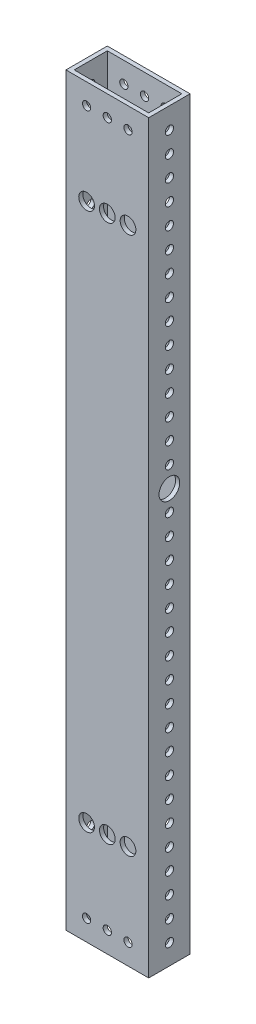
SolidWorks part; units mm, degrees
ref_plane "Front Plane" through (0, 0, 0) normal (0, 0, 1) x (1, 0, 0)
ref_plane "Top Plane" through (0, 0, 0) normal (0, 1, 0) x (1, 0, 0)
ref_plane "Right Plane" through (0, 0, 0) normal (1, 0, 0) x (0, 0, -1)
sketch "Sketch1" plane through (0, 0, 0) normal (0, 1, 0) x (1, 0, 0)
  line L1 (-46.8721, 24.2038) -> (3.9279, 24.2038)
  line L2 (-46.8721, 24.2038) -> (-46.8721, -1.1962)
  line L3 (-46.8721, -1.1962) -> (3.9279, -1.1962)
  line L4 (3.9279, 24.2038) -> (3.9279, -1.1962)
  line L5 (-46.8721, 24.2038) -> (3.9279, -1.1962) construction
  line L6 (-46.8721, -1.1962) -> (3.9279, 24.2038) construction
  line L7 (-44.3321, 21.6638) -> (1.3879, 21.6638)
  line L8 (-44.3321, 21.6638) -> (-44.3321, 1.3438)
  line L9 (-44.3321, 1.3438) -> (1.3879, 1.3438)
  line L10 (1.3879, 21.6638) -> (1.3879, 1.3438)
  line L11 (-44.3321, 21.6638) -> (1.3879, 1.3438) construction
  line L12 (-44.3321, 1.3438) -> (1.3879, 21.6638) construction
  point P0 (-21.4721, 11.5038)
  point P5 (-21.4721, 11.5038)
  dimension "D1" = 2.54
  dimension "D2" = 2.54
  dimension "D3" = 25.4
  dimension "D4" = 50.8
extrude "Boss-Extrude1" add sketch "Sketch1" along normal blind 457.2
sketch "Sketch3" plane through (3.9279, 0, 0) normal (1, 0, 0) x (0, 0, -1)
  line L0 (-1.1962, 457.2) -> (24.2038, 457.2) construction
  line L2 (24.2038, 457.2) -> (24.2038, 0) construction
  circle A0 centre (11.5038, 444.246) radius 2.54
  circle A1 centre (11.5038, 431.546) radius 2.54
  circle A2 centre (11.5038, 418.846) radius 2.54
  circle A3 centre (11.5038, 406.146) radius 2.54
  circle A4 centre (11.5038, 393.446) radius 2.54
  circle A5 centre (11.5038, 380.746) radius 2.54
  circle A6 centre (11.5038, 368.046) radius 2.54
  circle A7 centre (11.5038, 355.346) radius 2.54
  circle A8 centre (11.5038, 342.646) radius 2.54
  circle A9 centre (11.5038, 329.946) radius 2.54
  circle A10 centre (11.5038, 317.246) radius 2.54
  circle A11 centre (11.5038, 304.546) radius 2.54
  circle A12 centre (11.5038, 291.846) radius 2.54
  circle A13 centre (11.5038, 279.146) radius 2.54
  circle A14 centre (11.5038, 266.446) radius 2.54
  circle A16 centre (11.5038, 241.046) radius 2.54
  circle A17 centre (11.5038, 228.346) radius 2.54
  circle A18 centre (11.5038, 215.646) radius 2.54
  circle A19 centre (11.5038, 202.946) radius 2.54
  circle A20 centre (11.5038, 190.246) radius 2.54
  circle A21 centre (11.5038, 177.546) radius 2.54
  circle A22 centre (11.5038, 164.846) radius 2.54
  circle A23 centre (11.5038, 152.146) radius 2.54
  circle A24 centre (11.5038, 139.446) radius 2.54
  circle A25 centre (11.5038, 126.746) radius 2.54
  circle A26 centre (11.5038, 114.046) radius 2.54
  circle A27 centre (11.5038, 101.346) radius 2.54
  circle A28 centre (11.5038, 88.646) radius 2.54
  circle A29 centre (11.5038, 75.946) radius 2.54
  circle A30 centre (11.5038, 63.246) radius 2.54
  circle A31 centre (11.5038, 50.546) radius 2.54
  circle A32 centre (11.5038, 37.846) radius 2.54
  circle A33 centre (11.5038, 25.146) radius 2.54
  circle A34 centre (11.5038, 12.446) radius 2.54
  circle A35 centre (11.5038, 253.746) radius 2.54 [skipped]
  circle A36 centre (11.5038, 253.746) radius 6.35
  dimension "D3" = 5.08
  dimension "D1" = 12.954
  dimension "D2" = 12.7
  dimension "D4" = 35
extrude "Cut-Extrude1" cut sketch "Sketch3" against normal blind 457.2
sketch "Sketch4" plane through (0, 0, -24.2038) normal (0, 0, -1) x (-1, 0, 0)
  line L0 (-3.9279, 457.2) -> (46.8721, 457.2) construction
  line L1 (46.8721, 457.2) -> (46.8721, 0) construction
  line L2 (-3.9279, 457.2) -> (-3.9279, 0) construction
  line L4 (-3.9279, 228.6) -> (46.8721, 228.6) construction
  circle A0 centre (34.1721, 444.5) radius 2.54
  circle A1 centre (21.4721, 444.5) radius 2.54
  circle A2 centre (8.7721, 444.5) radius 2.54
  circle A3 centre (8.7721, 393.7) radius 4.826
  circle A4 centre (21.4721, 393.7) radius 4.826
  circle A5 centre (34.1721, 393.7) radius 4.826
  circle A6 centre (34.1721, 12.7) radius 2.54
  circle A7 centre (21.4721, 12.7) radius 2.54
  circle A8 centre (8.7721, 12.7) radius 2.54
  circle A9 centre (34.1721, 63.5) radius 4.826
  circle A10 centre (21.4721, 63.5) radius 4.826
  circle A11 centre (8.7721, 63.5) radius 4.826
  dimension "D1" = 5.08
  dimension "D6" = 9.652
  dimension "D2" = 12.7
  dimension "D3" = 12.7
  dimension "D5" = 50.8
  dimension "D7" = 12.7
  dimension "D4" = 3
  dimension "D8" = 3
extrude "Cut-Extrude3" cut sketch "Sketch4" against normal blind 457.2
